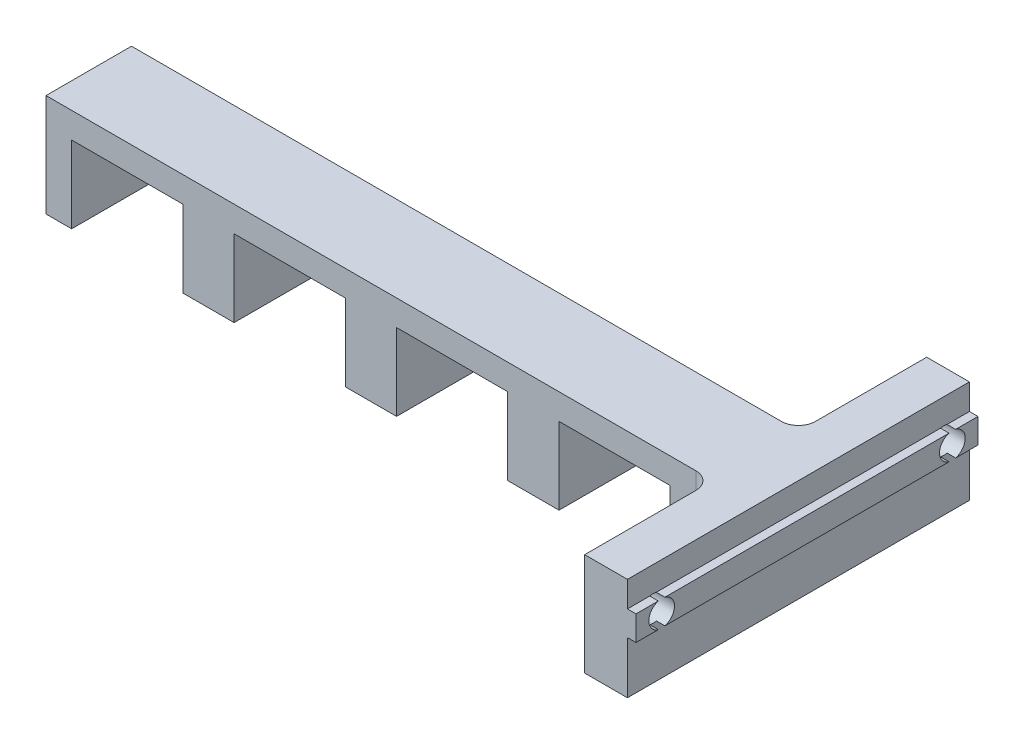
SolidWorks part; units mm, degrees
ref_plane "Front Plane" through (0, 0, 0) normal (0, 0, 1) x (1, 0, 0)
ref_plane "Top Plane" through (0, 0, 0) normal (0, 1, 0) x (1, 0, 0)
ref_plane "Right Plane" through (0, 0, 0) normal (1, 0, 0) x (0, 0, -1)
sketch "Esquisse1" plane through (0, 0, 0) normal (0, 0, 1) x (1, 0, 0)
  line L0 (3, 0) -> (3, 9)
  line L1 (3, 9) -> (16, 9)
  line L2 (16, 9) -> (16, 0)
  line L3 (16, 0) -> (22, 0)
  line L4 (22, 0) -> (22, 9)
  line L5 (22, 9) -> (35, 9)
  line L6 (35, 9) -> (35, 0)
  line L7 (35, 0) -> (41, 0)
  line L8 (41, 0) -> (41, 9)
  line L9 (41, 9) -> (54, 9)
  line L10 (54, 9) -> (54, 0)
  line L11 (54, 0) -> (60, 0)
  line L12 (83, 0) -> (83, 12)
  line L13 (83, 12) -> (0, 12)
  line L14 (0, 12) -> (0, 0)
  line L15 (0, 0) -> (3, 0)
  line L16 (60, 0) -> (60, 9)
  line L17 (60, 9) -> (73, 9)
  line L18 (73, 9) -> (73, 0)
  line L19 (73, 0) -> (83, 0)
  dimension "D1" = 13
  dimension "D2" = 6
  dimension "D3" = 6
  dimension "D4" = 6
  dimension "D5" = 3
  dimension "D6" = 10
  dimension "D7" = 12
  dimension "D8" = 3
extrude "Main" add sketch "Esquisse1" along normal mid plane 10
sketch "Sketch1" plane through (0, 0, 0) normal (0, 0, 1) x (1, 0, 0)
  line L0 (78, 12) -> (83, 12)
  line L1 (83, 12) -> (0, 12) construction
  line L2 (83, 12) -> (83, 9)
  line L3 (83, 0) -> (83, 12) construction
  line L4 (83, 9) -> (84, 9)
  line L5 (84, 9) -> (84, 6.1)
  line L6 (84, 6.1) -> (83, 6.1)
  line L7 (83, 6.1) -> (83, 0)
  line L8 (83, 0) -> (78, 0)
  line L9 (73, 0) -> (83, 0) construction
  line L10 (78, 0) -> (78, 12)
  dimension "D1" = 5
  dimension "D2" = 2.9
  dimension "D3" = 3
  dimension "D4" = 1
extrude "MakerBeamFix" add sketch "Sketch1" along normal mid plane 40
sketch "Sketch2" plane through (84, 0, 0) normal (1, 0, 0) x (0, 0, -1)
  line L0 (-20, 6.1) -> (-20, 9) construction
  line L1 (20, 6.1) -> (20, 9) construction
  circle A0 centre (-17, 7.55) radius 1.5
  circle A1 centre (17, 7.55) radius 1.5
  point P4 (-20, 7.55)
  point P5 (0, 0)
  dimension "D3" = 3
  dimension "D1" = 3
  dimension "D2" = 3
  dimension "D4" = 34
extrude "MakerBeamFixHole" cut sketch "Sketch2" against normal blind 30
fillet "Fillet1" radius 2 2 edges at (78, 6, -5) (78, 6, 5)
